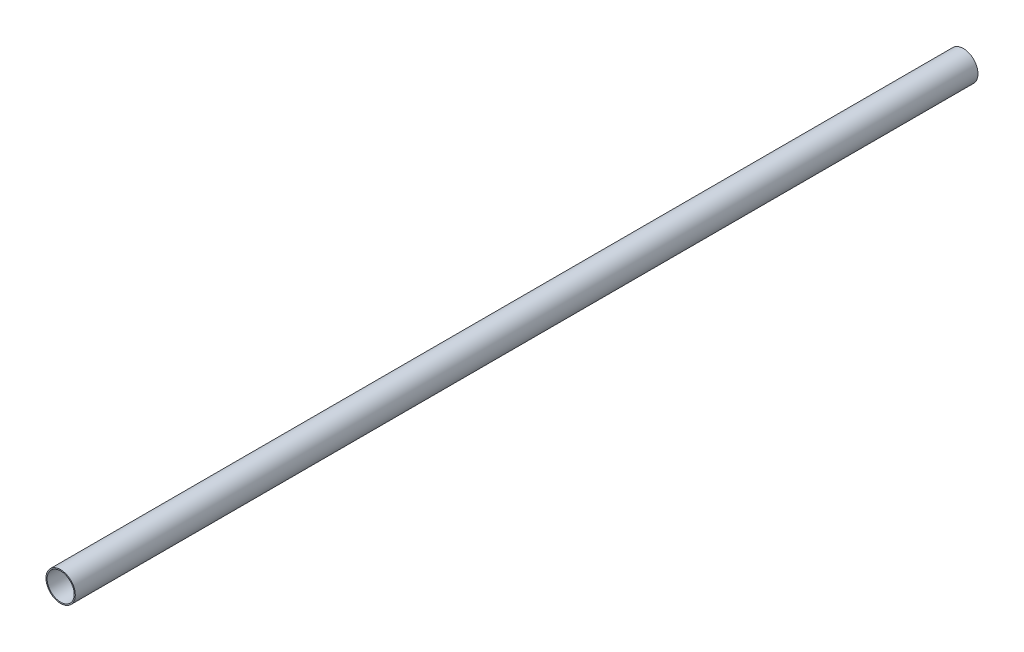
SolidWorks part; units mm, degrees
material "6061 Alloy"
ref_plane "Front Plane" through (0, 0, 0) normal (0, 0, 1) x (1, 0, 0)
ref_plane "Top Plane" through (0, 0, 0) normal (0, 1, 0) x (1, 0, 0)
ref_plane "Right Plane" through (0, 0, 0) normal (1, 0, 0) x (0, 0, -1)
sketch "Sketch1" plane through (0, 0, 0) normal (0, 0, 1) x (1, 0, 0)
  circle A0 centre (390.7614, 31.0815) radius 6.5
  circle A1 centre (390.7614, 31.0815) radius 6
extrude "Boss-Extrude1" add sketch "Sketch1" along normal blind 400
